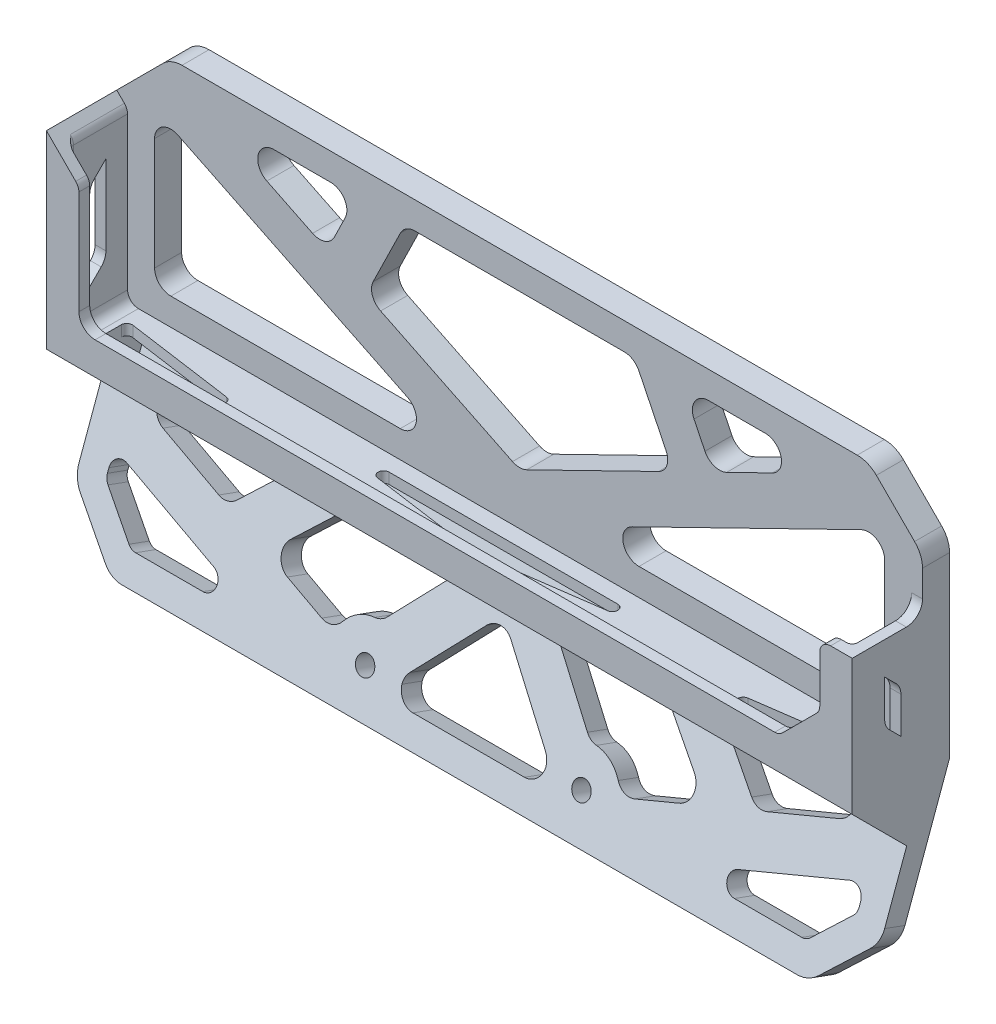
SolidWorks part; units mm, degrees
ref_plane "Front Plane" through (0, 0, 0) normal (0, 0, 1) x (1, 0, 0)
ref_plane "Top Plane" through (0, 0, 0) normal (0, 1, 0) x (1, 0, 0)
ref_plane "Right Plane" through (0, 0, 0) normal (1, 0, 0) x (0, 0, -1)
sketch "Sketch1" plane through (0, 0, 0) normal (0, 0, 1) x (1, 0, 0)
  line L1 (0, 0) -> (149, 0)
  line L2 (0, 0) -> (0, 15)
  line L3 (0, 15) -> (149, 15)
  line L4 (149, 0) -> (149, 15)
  line L5 (0, 15) -> (149, 15)
  line L6 (0, 15) -> (0, 75)
  line L7 (0, 75) -> (149, 75)
  line L8 (149, 15) -> (149, 75)
  circle A0 centre (45, 7.5) radius 1.65
  circle A1 centre (104, 7.5) radius 1.65
  dimension "D4" = 3.3
  dimension "D5" = 3.3
  dimension "D1" = 15
  dimension "D2" = 149
  dimension "D3" = 60
  dimension "D6" = 45
  dimension "D7" = 45
  dimension "D8" = 149
extrude "Boss-Extrude1" add sketch "Sketch1" along normal blind 5 contours L3 L8 L7 L6 | L1 L4 L3 L2 region at (74.5, 7.5, 0) region at (74.5, 45, 0)
fillet "Fillet1" radius 10 2 edges at (149, 0, 2.5) (0, 0, 2.5)
sketch "Sketch2" plane through (0, 0, 5) normal (0, 0, 1) x (1, 0, 0)
  line L0 (149, 10) -> (149, 75) construction
  line L1 (0, 75) -> (2, 75)
  line L2 (0, 75) -> (0, 30)
  line L3 (0, 30) -> (149, 30)
  line L4 (149, 55) -> (149, 30)
  line L5 (2, 73) -> (2, 32)
  line L6 (2, 32) -> (147, 32)
  line L7 (147, 55) -> (147, 32)
  line L9 (2, 73) -> (2, 75)
  line L12 (0, 75) -> (149, 75) construction
  line L13 (2, 73) -> (147, 73) construction
  line L14 (147, 73) -> (147, 32) construction
  line L19 (149, 75) -> (149, 30) construction
  line L20 (0, 75) -> (149, 75) construction
  line L23 (149, 55) -> (147, 55)
  dimension "D1" = 45
  dimension "D2" = 2
  dimension "D3" = 20
extrude "Boss-Extrude2" add sketch "Sketch2" along normal blind 11
sketch "Sketch3" plane through (0, 0, 16) normal (0, 0, 1) x (1, 0, 0)
  line L0 (149, 30) -> (149, 55) construction
  line L1 (0, 75) -> (0, 30) construction
  line L2 (0, 30) -> (149, 30) construction
  line L3 (149, 30) -> (149, 55)
  line L4 (0, 75) -> (0, 30)
  line L5 (0, 30) -> (149, 30)
  line L6 (6, 75) -> (6, 36)
  line L7 (6, 36) -> (143, 36)
  line L8 (143, 36) -> (143, 55)
  line L9 (6, 75) -> (0, 75)
  line L10 (143, 55) -> (149, 55)
  dimension "D1" = 6
extrude "Boss-Extrude3" add sketch "Sketch3" along normal blind 2 contours L6 L7 L8 L10 L3 L5 L4 L9
chamfer "Chamfer1" distance 7.5 angle 45 1 edges at (143, 36, 17)
sketch "Sketch4" plane through (0, 0, 0) normal (-1, 0, 0) x (0, 0, 1)
  line L0 (18, 30) -> (5, 18)
  line L1 (5, 10) -> (5, 30) construction
  line L2 (18, 30) -> (5, 30)
  line L3 (5, 30) -> (5, 18)
extrude "Boss-Extrude4" add sketch "Sketch4" against normal blind 5 contours L0 L3 L2
ref_plane "Plane1" through (74.5, 0, 0) normal (-1, 0, 0) x (0, 0, 1)
mirror "Mirror1" about plane through (74.5, 0, 0) normal (-1, 0, 0) of "Boss-Extrude4"
fillet "Fillet2" radius 3 3 edges at (74.5, 30, 5) (146.5, 18, 5) (2.5, 18, 5)
fillet "Fillet3" radius 3 1 edges at (6, 36, 17)
sketch "Sketch6" plane through (0, 0, 5) normal (0, 0, 1) x (1, 0, 0)
  line L0 (52.4102, 68.2432) -> (53.2691, 70)
  line L1 (142, 70) -> (7, 70)
  line L2 (7, 70) -> (7, 37)
  line L3 (7, 37) -> (142, 37)
  line L4 (142, 37) -> (142, 60)
  line L5 (96.5898, 68.2432) -> (95.7309, 70)
  line L6 (110.0867, 58.8504) -> (132.8927, 70)
  line L7 (149, 55) -> (149, 75)
  line L8 (149, 75) -> (2, 75)
  line L9 (2, 75) -> (2, 32)
  line L10 (2, 32) -> (147, 32)
  line L11 (147, 32) -> (147, 55)
  line L12 (147, 55) -> (149, 55)
  line L13 (149, 55) -> (149, 75)
  line L14 (149, 75) -> (2, 75)
  line L15 (2, 75) -> (2, 32)
  line L16 (2, 32) -> (147, 32)
  line L17 (147, 32) -> (147, 55)
  line L18 (147, 55) -> (149, 55)
  line L19 (142, 60) -> (142, 70)
  line L20 (144, 70) -> (7, 70) construction
  line L21 (144, 60) -> (144, 70) construction
  line L22 (142, 60) -> (144, 60) construction
  line L23 (46.1004, 55.3367) -> (74.5, 41.4524)
  line L24 (102.8996, 55.3367) -> (96.5898, 68.2432)
  line L25 (16.1073, 70) -> (38.9133, 58.8504)
  line L26 (74.5, 41.4524) -> (102.8996, 55.3367)
  line L27 (38.9133, 58.8504) -> (44.3642, 70)
  line L28 (110.0867, 58.8504) -> (104.6358, 70)
  line L29 (7, 65.5476) -> (65.3927, 37)
  line L30 (83.6073, 37) -> (142, 65.5476)
  line L31 (46.1004, 55.3367) -> (52.4102, 68.2432)
  arc A0 (144, 70) -> (144, 70) centre (144, 70) ccw
  arc A4 (149, 75) -> (149, 75) centre (144, 70) ccw construction
  dimension "D1" = 0
  dimension "D2" = 5
extrude "Cut-Extrude2" cut sketch "Sketch6" against normal blind 10 contours L29 L2 L3 | L25 L27 L1 | L31 L23 L26 L24 L5 L1 L0 | L28 L6 L1 | L30 L3 L4 L19 region at (74.5, 58.2366, 5) region at (33.1283, 66.2835, 5) region at (115.8717, 66.2835, 5) region at (26.4642, 46.5159, 5) region at (122.5358, 46.5159, 5)
fillet "Fillet5" radius 3 17 edges at (104.6358, 70, 2.5) (132.8927, 70, 2.5) (110.0867, 58.8504, 2.5) (142, 65.5476, 2.5) (83.6073, 37, 2.5) (16.1073, 70, 2.5) (44.3642, 70, 2.5) (38.9133, 58.8504, 2.5) (95.7309, 70, 2.5) (53.2691, 70, 2.5) (65.3927, 37, 2.5) (7, 65.5476, 2.5) (7, 37, 2.5) (74.5, 41.4524, 2.5) (46.1004, 55.3367, 2.5) (102.8996, 55.3367, 2.5) (142, 37, 2.5)
sketch "Sketch9" plane through (149, 0, 0) normal (1, 0, 0) x (0, 0, -1)
  line L1 (-18, 30) -> (0, 30)
  line L2 (-18, 30) -> (-18, 0)
  line L3 (-18, 0) -> (0, 0)
  line L4 (0, 30) -> (0, 0)
extrude "Cut-Extrude3" cut sketch "Sketch9" against normal through all
sketch "Sketch12" plane through (149, 0, 0) normal (1, 0, 0) x (0, 0, -1)
  line L0 (0, 30) -> (-12.375, -4)
  line L1 (0, 30) -> (0, 75) construction
  line L2 (-4.2567, 30) -> (-16.1338, -2.6319)
  line L3 (-16.1338, -2.6319) -> (-12.375, -4)
  line L4 (0, 30) -> (-4.2567, 30)
  line L5 (0, 30) -> (-18, 30) construction
  line L6 (-3.7588, 31.3681) -> (-16.1338, -2.6319) construction
  dimension "D1" = 20
  dimension "D2" = 34
  dimension "D3" = 4
extrude "Boss-Extrude5" add sketch "Sketch12" against normal up to surface (149 mm away) up to face at (0, 52.5, 9)
chamfer "Chamfer2" distance 10 angle 45 2 edges at (149, -3.316, 14.2544) (0, -3.316, 14.2544)
sketch "Sketch13" plane through (0, 0, 0) normal (-1, 0, 0) x (0, 0, 1)
  line L0 (18, 30) -> (7.9241, 19.9241)
  line L1 (4.2567, 30) -> (12.7136, 6.765) construction
  line L2 (4.2567, 30) -> (18, 30) construction
  line L3 (4.2567, 30) -> (12.7136, 6.765)
  line L4 (4.2567, 30) -> (18, 30)
  line M3 (12.7136, 6.765) -> (4.2567, 30)
  line M4 (4.2567, 30) -> (18, 30)
extrude "Boss-Extrude6" add sketch "Sketch13" against normal blind 5 contours L0 M4 M3 region at (0, 26.6414, 10.0603)
sketch "Sketch14" plane through (0, 4.8774, 13.4006) normal (0, 0.342, 0.9397) x (1, 0, 0)
  line L1 (74.5, 9.9) -> (74.5, -9.9) construction
  line L2 (10, -7.9913) -> (139, -7.9913) construction
  circle A0 centre (54.5, -0.4913) radius 1.7
  circle A1 centre (94.5, -0.4913) radius 1.7
  dimension "D1" = 3.4
  dimension "D2" = 3.4
  dimension "D3" = 20
  dimension "D4" = 20
  dimension "D5" = 7.5
  dimension "D6" = 7.5
extrude "Cut-Extrude4" cut sketch "Sketch14" against normal blind 5
chamfer "Chamfer3" distance 10 angle 45 2 edges at (149, 75, 2.5) (0, 75, 9)
mirror "Mirror2" about plane through (74.5, 0, 0) normal (-1, 0, 0) of "Boss-Extrude6"
sketch "Sketch15" plane through (0, 0, 18) normal (0, 0, 1) x (1, 0, 0)
  line L0 (0, 65) -> (6, 59)
  line L1 (6, 71) -> (6, 39) construction
  line L2 (6, 71) -> (0, 65) construction
  line L3 (6, 71) -> (6, 39)
  line L4 (6, 71) -> (0, 65)
  line M1 (6, 39) -> (6, 71)
  line M2 (6, 71) -> (0, 65)
extrude "Cut-Extrude5" cut sketch "Sketch15" against normal up to surface (13 mm away) contours L0 M2 M1 region at (4, 65, 18) up to face at (35.7183, 65.3568, 5)
fillet "Fillet6" radius 5 3 edges at (149, 65, 2.5) (139, 75, 2.5) (10, 75, 2.5)
fillet "Fillet7" radius 5 4 edges at (149, 6.081, 10.8342) (139, -3.316, 14.2544) (10, -3.316, 14.2544) (0, 6.081, 10.8342)
sketch "Sketch16" plane through (0, 32, 0) normal (0, 1, 0) x (1, 0, 0)
  line L0 (144, -13) -> (144, -8)
  line L1 (144, -8) -> (5, -8)
  line L2 (5, -8) -> (5, -13)
  line L3 (5, -13) -> (144, -13)
  line L4 (147, -5) -> (2, -5)
  line L5 (2, -5) -> (2, -16)
  line L6 (2, -16) -> (147, -16)
  line L7 (147, -16) -> (147, -5)
  line L8 (147, -5) -> (2, -5)
  line L9 (2, -5) -> (2, -16)
  line L10 (2, -16) -> (147, -16)
  line L11 (147, -16) -> (147, -5)
  line L12 (74.5, -13) -> (74.5, -9.9469) construction
  line L13 (74.5, -9.9469) -> (3.7611, -9.9469) construction
  line L14 (39.1306, -8) -> (74.5, -13)
  line L15 (109.8694, -8) -> (74.5, -13)
  line L16 (144, -8) -> (108.6306, -13)
  line L17 (5, -8) -> (40.3694, -13)
  dimension "D1" = 0
  dimension "D2" = 3
extrude "Cut-Extrude8" cut sketch "Sketch16" against normal blind 2 contours L0 L16 L3 | L15 L1 L14 | L17 L2 L3 region at (132.2102, 32, 11.3333) region at (74.5, 32, 9.6667) region at (16.7898, 32, 11.3333)
fillet "Fillet8" radius 1 9 edges at (74.5, 31, 13) (108.6306, 31, 13) (144, 31, 13) (144, 31, 8) (40.3694, 31, 13) (5, 31, 13) (5, 31, 8) (39.1306, 31, 8) (109.8694, 31, 8)
sketch "Sketch17" plane through (0, 4.8774, 13.4006) normal (0, 0.342, 0.9397) x (1, 0, 0)
  line L0 (122.1123, 10.8881) -> (123.4257, 9.5747)
  line L1 (33.8579, 6.5447) -> (48.0581, 1.3505)
  line L2 (37.7345, 21.7349) -> (10, 21.7349)
  line L3 (123.4257, 9.5747) -> (137.6259, 14.7689)
  line L4 (99.9518, 21.7349) -> (79.881, 21.7349)
  line L5 (69.119, 21.7349) -> (49.0482, 21.7349)
  line L10 (60.7161, -2.9913) -> (88.2839, -2.9913)
  line L11 (112.3602, -2.9913) -> (136.9289, -2.9913)
  line L12 (26.8877, 10.8881) -> (25.5743, 9.5747)
  line L13 (46.2197, 18.9065) -> (49.0482, 21.7349)
  line L14 (61.0687, 0.8286) -> (74.5, 15.7549)
  line L15 (8.6259, 7.2557) -> (36.6398, -2.9913)
  line L16 (112.3602, -2.9913) -> (140.3741, 7.2557)
  line L17 (11.3741, 14.7689) -> (25.5743, 9.5747)
  line L18 (100.9419, 1.3505) -> (115.1421, 6.5447)
  line L19 (11.3741, 14.7689) -> (10, 15.2715)
  line L20 (136.9289, -2.9913) -> (144, 4.0798)
  line L21 (144, 4.0798) -> (144, 11.0123)
  line L22 (144, 11.0123) -> (139, 11.0123)
  line L23 (139, 11.0123) -> (139, 21.7349)
  line L24 (139, 21.7349) -> (10, 21.7349)
  line L25 (10, 21.7349) -> (10, 11.0123)
  line L26 (10, 11.0123) -> (5, 11.0123)
  line L27 (5, 11.0123) -> (5, 4.0798)
  line L28 (5, 4.0798) -> (12.0711, -2.9913)
  line L29 (12.0711, -2.9913) -> (136.9289, -2.9913)
  line L30 (136.9289, -2.9913) -> (144, 4.0798)
  line L31 (144, 4.0798) -> (144, 8.582)
  line L33 (139, 15.2715) -> (139, 21.7349)
  line L34 (139, 21.7349) -> (111.2655, 21.7349)
  line L35 (10, 21.7349) -> (10, 15.2715)
  line L37 (5, 8.582) -> (5, 4.0798)
  line L38 (5, 4.0798) -> (12.0711, -2.9913)
  line L39 (12.0711, -2.9913) -> (36.6398, -2.9913)
  line L40 (8.6259, 7.2557) -> (5, 8.582)
  line L41 (140.3741, 7.2557) -> (144, 8.582)
  line L42 (137.6259, 14.7689) -> (139, 15.2715)
  line L43 (74.5, 15.7549) -> (87.9313, 0.8286)
  line L44 (55.1219, 6.1798) -> (69.119, 21.7349)
  line L45 (79.881, 21.7349) -> (93.8781, 6.1798)
  line L46 (122.1123, 10.8881) -> (111.2655, 21.7349)
  line L47 (33.8579, 6.5447) -> (46.2197, 18.9065)
  line L48 (115.1421, 6.5447) -> (102.7803, 18.9065)
  line L49 (26.8877, 10.8881) -> (37.7345, 21.7349)
  line L50 (102.7803, 18.9065) -> (99.9518, 21.7349)
  circle A13 centre (94.5, -0.4913) radius 6.7
  arc A14 (100.9419, 1.3505) -> (93.8781, 6.1798) centre (94.5, -0.4913) ccw
  circle A16 centre (54.5, -0.4913) radius 6.7
  arc A17 (60.7161, -2.9913) -> (61.0687, 0.8286) centre (54.5, -0.4913) ccw
  arc A21 (55.1219, 6.1798) -> (48.0581, 1.3505) centre (54.5, -0.4913) ccw
  arc A22 (87.9313, 0.8286) -> (88.2839, -2.9913) centre (94.5, -0.4913) ccw
  dimension "D1" = 5
  dimension "D2" = 5
  dimension "D3" = 5
extrude "Cut-Extrude9" cut sketch "Sketch17" against normal through all
fillet "Fillet9" radius 3 4 edges at (88.2839, 1.3825, 12.5443) (87.9313, 4.972, 11.2378) (60.7161, 1.3825, 12.5443) (61.0687, 4.972, 11.2378)
fillet "Fillet10" radius 3 11 edges at (100.9419, 5.4624, 11.0593) (93.8781, 10.0005, 9.4076) (115.1421, 10.3434, 9.2828) (99.9518, 24.6175, 4.0874) (79.881, 24.6175, 4.0874) (33.8579, 10.3434, 9.2828) (49.0482, 24.6175, 4.0874) (69.119, 24.6175, 4.0874) (55.1219, 10.0005, 9.4076) (48.0581, 5.4624, 11.0593) (74.5, 18.9982, 6.1327)
fillet "Fillet11" radius 3 8 edges at (123.4257, 13.1907, 8.2465) (111.2655, 24.6175, 4.0874) (139, 24.6175, 4.0874) (139, 18.5439, 6.298) (10, 18.5439, 6.298) (25.5743, 13.1907, 8.2465) (37.7345, 24.6175, 4.0874) (10, 24.6175, 4.0874)
fillet "Fillet12" radius 2 2 edges at (112.3602, 1.3825, 12.5443) (36.6398, 1.3825, 12.5443)
fillet "Fillet13" radius 2 6 edges at (136.9289, 1.3825, 12.5443) (144, 8.0271, 10.1258) (144, 12.2578, 8.586) (5, 8.0271, 10.1258) (5, 12.2578, 8.586) (12.0711, 1.3825, 12.5443)
sketch "Sketch18" plane through (149, 0, 0) normal (1, 0, 0) x (0, 0, -1)
  line L12 (-9, 36) -> (-9, 51)
  line L13 (-12, 36) -> (-9, 36)
  line L14 (-12, 51) -> (-12, 36)
  line L15 (-9, 51) -> (-12, 51)
  line L16 (-9, 36) -> (-9, 51)
  line L17 (-12, 36) -> (-9, 36)
  line L18 (-12, 51) -> (-12, 36)
  line L19 (-9, 51) -> (-12, 51)
  dimension "D1" = 4
extrude "Cut-Extrude10" cut sketch "Sketch18" against normal blind 2
chamfer "Chamfer5" distance 5 angle 45 2 edges at (148, 51, 9) (148, 36, 12)
sketch "Sketch19" plane through (0, 0, 0) normal (-1, 0, 0) x (0, 0, 1)
  line L8 (9, 59) -> (9, 36)
  line L9 (12, 59) -> (9, 59)
  line L10 (12, 36) -> (12, 59)
  line L11 (9, 36) -> (12, 36)
  line L12 (9, 59) -> (9, 36)
  line L13 (12, 59) -> (9, 59)
  line L14 (12, 36) -> (12, 59)
  line L15 (9, 36) -> (12, 36)
  dimension "D1" = 4
extrude "Cut-Extrude11" cut sketch "Sketch19" against normal blind 2
chamfer "Chamfer6" distance 5 angle 45 2 edges at (1, 59, 12) (1, 36, 9)
fillet "Fillet14" radius 3 4 edges at (148, 46, 9) (148, 41, 12) (1, 54, 12) (1, 41, 9)
fillet "Fillet15" radius 1 rebuild error yes
fillet "Fillet16" radius 1 rebuild error yes
fillet "Fillet17" radius 2 2 edges at (147, 32, 10.5) (2, 32, 10.5)
fillet "Fillet18" radius 2 2 edges at (2, 63, 10.5) (6, 59, 17)
fillet "Fillet19" radius 3 1 edges at (148, 55, 5)
fillet "Fillet20" radius 1 6 edges at (1.8478, 62.9369, 16) (2, 48.0858, 16) (2.5858, 32.5858, 16) (74.5, 32, 16) (146.4142, 32.5858, 16) (147, 44.5, 16)
fillet "Fillet21" radius 2 3 edges at (135.5, 36, 17) (143, 43.5, 17) (143, 55, 17)
sketch "Sketch21" plane through (2, 0, 0) normal (1, 0, 0) x (0, 0, -1)
  line L0 (-15, 34) -> (-5, 34) construction
  line L1 (-10, 34) -> (-5.8031, 34)
  line L2 (-10, 34) -> (-10, 61.1467)
  line L3 (-10, 61.1467) -> (-5.8031, 61.1467)
  line L4 (-5.8031, 34) -> (-5.8031, 61.1467)
